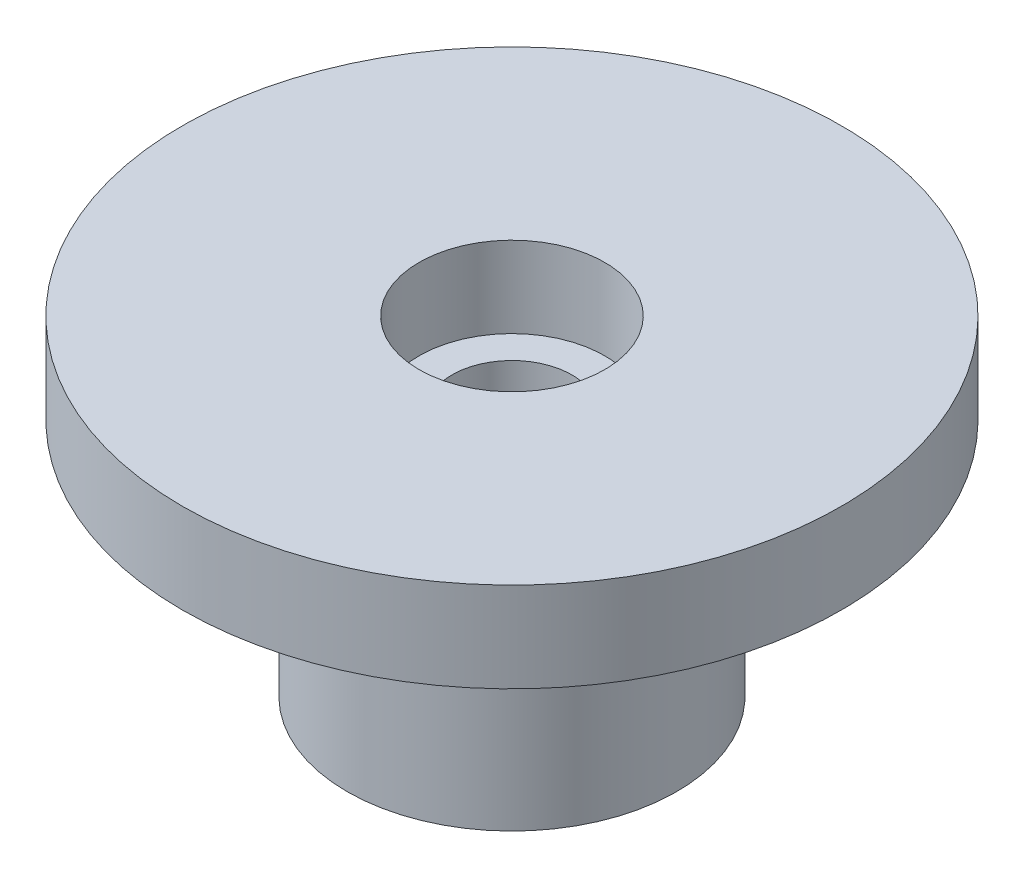
SolidWorks part; units mm, degrees
ref_plane "前视基准面" through (0, 0, 0) normal (0, 0, 1) x (1, 0, 0)
ref_plane "上视基准面" through (0, 0, 0) normal (0, 1, 0) x (1, 0, 0)
ref_plane "右视基准面" through (0, 0, 0) normal (1, 0, 0) x (0, 0, -1)
other "Configuration Table"
sketch "草图1" plane through (0, 0, 0) normal (0, 1, 0) x (1, 0, 0)
  circle A0 centre (0, 0) radius 5.5
  circle A1 centre (0, 0) radius 11
  dimension "D1" = 5.5
  dimension "D2" = 22
extrude "凸台-拉伸3" add sketch "草图1" along normal mid plane 22 contours A1
extrude "切除-拉伸1" cut sketch "草图1<10>" along normal mid plane 16
sketch "草图1<10>" plane through (0, 0, 0) normal (0, 1, 0) x (1, 0, 0) same geometry as "草图1"
sketch "草图2" plane through (0, 11, 0) normal (0, 1, 0) x (1, 0, 0)
  circle A0 centre (0, 0) radius 3.1
  circle A1 centre (0, 0) radius 2
  dimension "D1" = 4
  dimension "D2" = 6.2
extrude "切除-拉伸2" cut sketch "草图2" against normal through all contours A1
extrude "切除-拉伸3" cut sketch "草图2<3>" against normal blind 2.7 contours A0
sketch "草图2<3>" plane through (0, 11, 0) normal (0, 1, 0) x (1, 0, 0) same geometry as "草图2"
extrude "切除-拉伸4" cut sketch "草图2<4>" along normal blind 2.7 from surface contours A0 starting at face at (0, -11, 2)
sketch "草图2<4>" plane through (0, 11, 0) normal (0, 1, 0) x (1, 0, 0) same geometry as "草图2"
sketch "草图3" plane through (0, 0, 0) normal (0, 1, 0) x (1, 0, 0)
  circle A0 centre (0, 0) radius 50
  dimension "D1" = 100
extrude "切除-拉伸5" cut sketch "草图3" against normal through all
